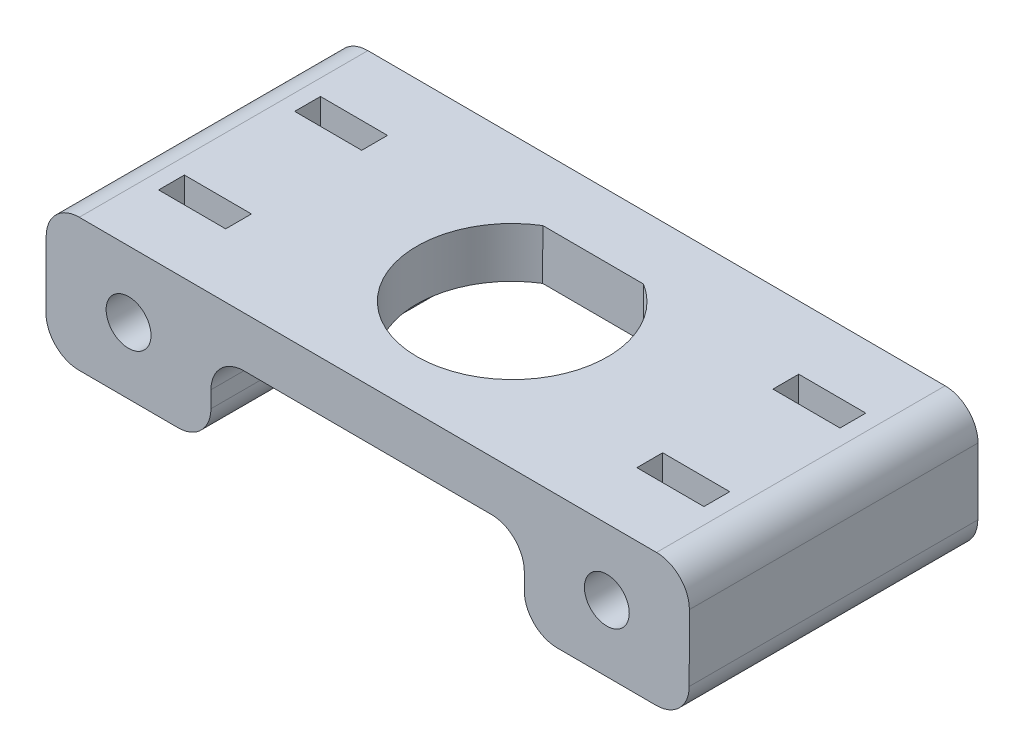
SolidWorks part; units mm, degrees
material "ABS"
ref_plane "Front Plane" through (0, 0, 0) normal (0, 0, 1) x (1, 0, 0)
ref_plane "Top Plane" through (0, 0, 0) normal (0, 1, 0) x (1, 0, 0)
ref_plane "Right Plane" through (0, 0, 0) normal (1, 0, 0) x (0, 0, -1)
sketch "Sketch1" plane through (0, 0, 0) normal (0, 0, 1) x (1, 0, 0)
  line L1 (-96.8239, -119.8414) -> (-47.2941, -119.9836)
  line L3 (-84.135, -123.7428) -> (-60.0051, -123.8121)
  line L8 (-96.8239, -119.8414) -> (-96.8532, -130.0563)
  line L9 (-96.8532, -130.0563) -> (-84.1533, -130.0928)
  line L10 (-84.1533, -130.0928) -> (-84.135, -123.7428)
  line L11 (-72.059, -119.9125) -> (-72.0701, -123.7775) construction
  line L12 (-60.0234, -130.1621) -> (-60.0051, -123.8121)
  line L13 (-47.3234, -130.1986) -> (-60.0234, -130.1621)
  line L14 (-47.2941, -119.9836) -> (-47.3234, -130.1986)
  dimension "D2" = 3.865
  dimension "D3" = 24.13
  dimension "D4" = 12.7
  dimension "D5" = 6.35
extrude "Boss-Extrude1" add sketch "Sketch1" along normal blind 22.225
sketch "Sketch2" plane through (-0.345, -120.1185, 0) normal (0.0029, 1, 0) x (1, -0.0029, 0)
  line L0 (-46.9492, 0) -> (-96.4792, -22.225) construction
  line L1 (-67.8371, -4.8775) -> (-75.5914, -4.8775)
  line L2 (-46.9492, -22.225) -> (-96.4792, -22.225) construction
  line L3 (-73.7565, -5.5125) -> (-75.9142, -5.5125) construction
  arc A0 (-75.5914, -4.8775) -> (-67.8371, -4.8775) centre (-71.7142, -11.1125) ccw
  dimension "D1" = 14.6844
  dimension "D2" = 0.635
extrude "Cut-Extrude1" cut sketch "Sketch2" against normal up to next
fillet "Fillet1" radius 2.54 8 edges at (-47.2941, -119.9836, 11.1125) (-47.3234, -130.1986, 11.1125) (-60.0234, -130.1621, 11.1125) (-96.8239, -119.8414, 11.1125) (-96.8532, -130.0563, 11.1125) (-84.1533, -130.0928, 11.1125) (-60.0051, -123.8121, 11.1125) (-84.135, -123.7428, 11.1125)
hole_wizard "#4 Clearance Hole1" positions "Sketch5" profile "Sketch4" hole size "#4" standard "ANSI Inch" end condition through all
sketch "Sketch5" plane through (0, 0, 22.225) normal (0, 0, 1) x (1, 0, 0)
  line L0 (-90.5033, -130.0746) -> (-90.4739, -119.8596) construction
  line L1 (-94.3132, -130.0636) -> (-86.6933, -130.0855) construction
  line L2 (-49.8341, -119.9763) -> (-94.2839, -119.8487) construction
  line L4 (-96.8312, -122.3813) -> (-96.8459, -127.5163) construction
  line L5 (-72.059, -119.9125) -> (-72.0701, -123.7775) construction
  line L6 (-81.5951, -123.7501) -> (-62.5451, -123.8048) construction
  point P10 (-90.4886, -124.9671)
  point P18 (-53.6587, -125.0729)
sketch "Sketch4" plane through (-90.4886, -124.9671, 22.225) normal (1, 0, 0) x (0, -1, 0)
  line L0 (0, 0) -> (0, 22.225)
  line L1 (0, 22.225) -> (1.7272, 22.225)
  line L2 (1.7272, 22.225) -> (1.7272, 0)
  line L5 (1.7272, 0) -> (0, 0)
  line L11 (0, -6.35) -> (0, 107.95) construction
  dimension "Thru Hole Dia." = 3.4544
  dimension "Thru Hole Depth" = 22.225
sketch "Sketch6" plane through (-0.345, -120.1185, 0) normal (0.0029, 1, 0) x (1, -0.0029, 0)
  line L0 (-92.7105, -17.345) -> (-92.7105, -15.3575)
  line L1 (-92.5105, -17.145) -> (-87.748, -17.145) construction
  line L2 (-92.5105, -17.145) -> (-92.5105, -15.5575) construction
  line L3 (-92.5105, -15.5575) -> (-87.748, -15.5575) construction
  line L4 (-87.748, -17.145) -> (-87.748, -15.5575) construction
  line L5 (-92.7105, -15.3575) -> (-87.548, -15.3575)
  line L6 (-87.548, -17.345) -> (-87.548, -15.3575)
  line L7 (-92.7105, -17.345) -> (-87.548, -17.345)
  line L8 (-96.4792, -11.1125) -> (-46.9492, -11.1125) construction
  line L9 (-96.4792, -22.225) -> (-96.4792, 0) construction
  line L10 (-46.9492, 0) -> (-46.9492, -22.225) construction
  line L11 (-71.7142, -11.1125) -> (-71.7142, 0) construction
  line L12 (-49.4892, 0) -> (-93.9392, 0) construction
  line L13 (-92.7105, -4.88) -> (-92.7105, -6.8675)
  line L14 (-92.7105, -4.88) -> (-87.548, -4.88)
  line L15 (-87.548, -4.88) -> (-87.548, -6.8675)
  line L16 (-92.7105, -6.8675) -> (-87.548, -6.8675)
  line L17 (-50.718, -4.88) -> (-50.718, -6.8675)
  line L18 (-50.718, -4.88) -> (-55.8805, -4.88)
  line L19 (-55.8805, -4.88) -> (-55.8805, -6.8675)
  line L20 (-50.718, -6.8675) -> (-55.8805, -6.8675)
  line L21 (-50.718, -15.3575) -> (-55.8805, -15.3575)
  line L22 (-50.718, -17.345) -> (-50.718, -15.3575)
  line L23 (-50.718, -17.345) -> (-55.8805, -17.345)
  line L24 (-55.8805, -17.345) -> (-55.8805, -15.3575)
  dimension "D1" = 0.2
extrude "Cut-Extrude2" cut sketch "Sketch6" against normal blind 8.255
